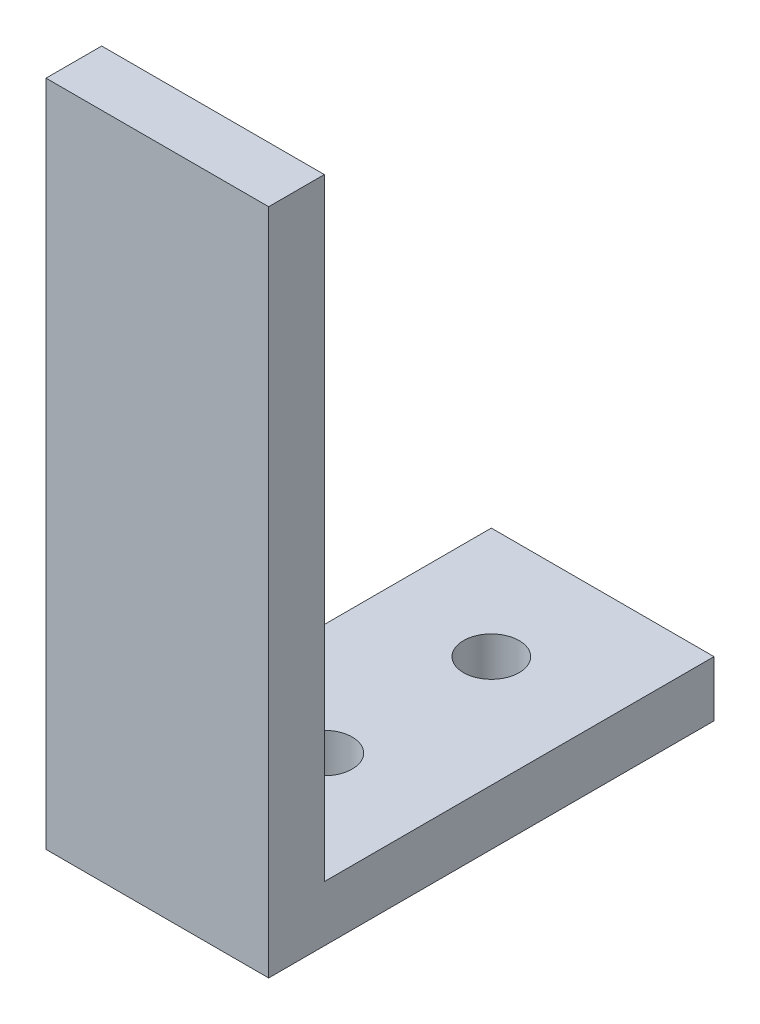
SolidWorks part; units mm, degrees
ref_plane "Front Plane" through (0, 0, 0) normal (0, 0, 1) x (1, 0, 0)
ref_plane "Top Plane" through (0, 0, 0) normal (0, 1, 0) x (1, 0, 0)
ref_plane "Right Plane" through (0, 0, 0) normal (1, 0, 0) x (0, 0, -1)
sketch "Sketch1" plane through (0, 0, 0) normal (1, 0, 0) x (0, 0, -1)
  line L0 (0, 76.2) -> (0, 0)
  line L1 (0, 0) -> (50.8, 0)
  line L2 (6.35, 76.2) -> (6.35, 6.35)
  line L3 (6.35, 6.35) -> (50.8, 6.35)
  line L4 (0, 76.2) -> (6.35, 76.2)
  line L5 (50.8, 6.35) -> (50.8, 0)
  dimension "D1" = 76.2
  dimension "D2" = 50.8
  dimension "D3" = 6.35
extrude "Boss-Extrude1" add sketch "Sketch1" along normal blind 25.4
sketch "Sketch2" plane through (0, 6.35, 0) normal (0, 1, 0) x (1, 0, 0)
  line L1 (25.4, 6.35) -> (0, 6.35) construction
  circle A0 centre (12.7, 38.1) radius 3.175
  circle A1 centre (12.7, 19.05) radius 3.175
  dimension "D1" = 12.7
  dimension "D2" = 31.75
  dimension "D3" = 6.35
extrude "Cut-Extrude1" cut sketch "Sketch2" against normal up to next
